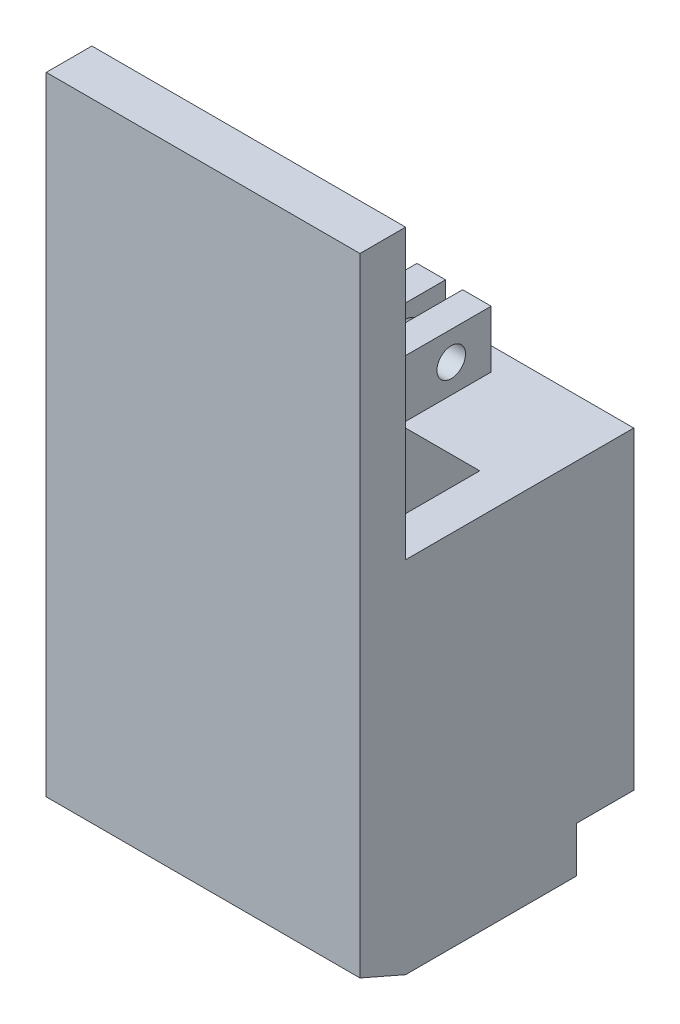
SolidWorks part; units mm, degrees
ref_plane "Plan de face" through (0, 0, 0) normal (0, 0, 1) x (1, 0, 0)
ref_plane "Plan de dessus" through (0, 0, 0) normal (0, 1, 0) x (1, 0, 0)
ref_plane "Plan de droite" through (0, 0, 0) normal (1, 0, 0) x (0, 0, -1)
sketch "Sketch1" plane through (0, 0, 0) normal (0, 0, 1) x (1, 0, 0)
  line L0 (-21, 0) -> (21, 0)
  line L1 (21, 0) -> (21, 42)
  line L2 (21, 42) -> (1.5, 42)
  line L3 (1.5, 42) -> (1.5, 58.5)
  line L4 (1.5, 58.5) -> (6.5, 58.5)
  line L5 (6.5, 58.5) -> (6.5, 48.5)
  line L6 (6.5, 48.5) -> (27.5, 48.5)
  line L7 (27.5, 48.5) -> (27.5, -6.5)
  line L8 (27.5, -6.5) -> (-27.5, -6.5)
  line L9 (0, 0) -> (0, -28.5179) construction
  line L10 (-27.5, 48.5) -> (-27.5, -6.5)
  line L11 (-6.5, 48.5) -> (-27.5, 48.5)
  line L12 (-6.5, 58.5) -> (-6.5, 48.5)
  line L13 (-1.5, 58.5) -> (-6.5, 58.5)
  line L14 (-1.5, 42) -> (-1.5, 58.5)
  line L15 (-21, 42) -> (-1.5, 42)
  line L16 (-21, 0) -> (-21, 42)
  point P13 (0, -6.5)
  dimension "D1" = 55
  dimension "D2" = 42
  dimension "D3" = 6.5
  dimension "D4" = 6.5
  dimension "D5" = 3
  dimension "D6" = 10
  dimension "D7" = 5
  dimension "D8" = 42
extrude "Boss-Extrude1" add sketch "Sketch1" along normal blind 40 contours L2 L3 L4 L5 L6 L7 L8 L10 L11 L12 L13 L14 L15 L16 L0 L1
sketch "Sketch2" plane through (-6.5, 0, 0) normal (-1, 0, 0) x (0, 0, 1)
  line L0 (20, 58.5) -> (20, 48.5) construction
  line L1 (40, 58.5) -> (0, 58.5) construction
  line L2 (40, 48.5) -> (0, 48.5) construction
  circle A0 centre (11, 53.5) radius 2.5
  circle A1 centre (29, 53.5) radius 2.5
  dimension "D1" = 5
  dimension "D2" = 9
  dimension "D3" = 5
extrude "Cut-Extrude1" cut sketch "Sketch2" against normal up to surface (13 mm away) up to face at (6.5, 53.5, 20)
sketch "Sketch3" plane through (0, 0, 0) normal (0, 0, -1) x (-1, 0, 0)
  line L0 (20.5, -6.5) -> (19.1705, -5.0058)
  line L1 (-27.5, -6.5) -> (27.5, -6.5) construction
  line L2 (16.9293, -4) -> (-3.9293, -4)
  line L4 (-7.5, -6.5) -> (-6.1705, -5.0058)
  line L5 (20.5, -6.5) -> (-7.5, -6.5)
  arc A0 (19.1705, -5.0058) -> (16.9293, -4) centre (16.9293, -7) ccw
  arc A1 (-6.1705, -5.0058) -> (-3.9293, -4) centre (-3.9293, -7) cw
  point P11 (18.2756, -4)
  point P14 (-5.2756, -4)
  dimension "D1" = 3
  dimension "D2" = 2.5
  dimension "D3" = 20
  dimension "D4" = 2
  dimension "D5" = 7
  dimension "D6" = 2
extrude "Cut-Extrude2" cut sketch "Sketch3" against normal blind 10
sketch "Sketch6" plane through (0, 0, 40) normal (0, 0, 1) x (1, 0, 0)
  line L0 (27.5, 48.5) -> (27.5, -6.5) construction
  line L1 (-27.5, -11) -> (27.5, -11)
  line L2 (-27.5, -11) -> (-27.5, 99)
  line L3 (-27.5, 99) -> (27.5, 99)
  line L4 (27.5, -11) -> (27.5, 99)
  line L7 (27.5, -6.5) -> (-27.5, -6.5) construction
  dimension "D1" = 4.5
  dimension "D2" = 110
  dimension "D3" = 55
extrude "Boss-Extrude8" add sketch "Sketch6" along normal blind 8 separate body
sketch "Sketch7" plane through (-6.5, 0, 0) normal (-1, 0, 0) x (0, 0, 1)
  line L0 (40, 48.5) -> (0, 48.5) construction
  line L1 (40, 58.5) -> (36, 58.5)
  line L2 (40, 58.5) -> (40, 48.5)
  line L3 (40, 48.5) -> (36, 48.5)
  line L4 (36, 58.5) -> (36, 48.5)
  line L5 (20, 58.5) -> (20, 48.5) construction
  line L6 (40, 58.5) -> (0, 58.5) construction
  line L7 (40, 48.5) -> (0, 48.5) construction
  line L8 (0, 48.5) -> (4, 48.5)
  line L9 (0, 58.5) -> (0, 48.5)
  line L10 (0, 58.5) -> (4, 58.5)
  line L11 (4, 58.5) -> (4, 48.5)
  dimension "D1" = 4
extrude "Cut-Extrude3" cut sketch "Sketch7" against normal up to surface (13 mm away) up to face at (6.5, 56, 29)
sketch "Sketch9" plane through (27.5, 0, 0) normal (1, 0, 0) x (0, 0, -1)
  line L0 (-40, -14.5) -> (-48, -11)
  line L1 (-40, -6.5) -> (-10, -6.5)
  line L2 (-48, -11) -> (-40, -11)
  line L3 (-40, -14.5) -> (-10, -14.5)
  line L4 (-10, -6.5) -> (-10, -14.5)
  line L5 (-48, -11) -> (-40, -11) construction
  line L6 (-40, -11) -> (-40, -6.5)
  line L7 (-78.4665, -39.45) -> (-78.4665, -5.15) construction
  dimension "D1" = 8
  dimension "D2" = 30
extrude "Boss-Extrude9" add sketch "Sketch9" against normal blind 20
extrude "Boss-Extrude10" add sketch "Sketch9<2>" against normal blind 7 from offset 48 offset against normal yes
sketch "Sketch9<2>" plane through (27.5, 0, 0) normal (1, 0, 0) x (0, 0, -1) same geometry as "Sketch9"
ref_plane "Plane1" through (16.5, 0, 0) normal (1, 0, 0) x (0, 0, -1)
sketch "Sketch10" plane through (16.5, 0, 0) normal (1, 0, 0) x (0, 0, -1)
  line L0 (-40, 68.5) -> (-20, 48.5)
  line L1 (-40, 48.5) -> (-40, 99) construction
  line L2 (-40, 48.5) -> (0, 48.5) construction
  dimension "D1" = 20
  dimension "D2" = 20
rib "Rib1" sketch "Sketch10" sketch "Sketch10" thickness 8 extrusion direction parallel to sketch draft on no parameters "D1"=8
ref_plane "Plane3" through (0, 0, 0) normal (1, 0, 0) x (0, 0, -1)
mirror "Mirror1" about plane through (0, 0, 0) normal (1, 0, 0) of "Rib1"
